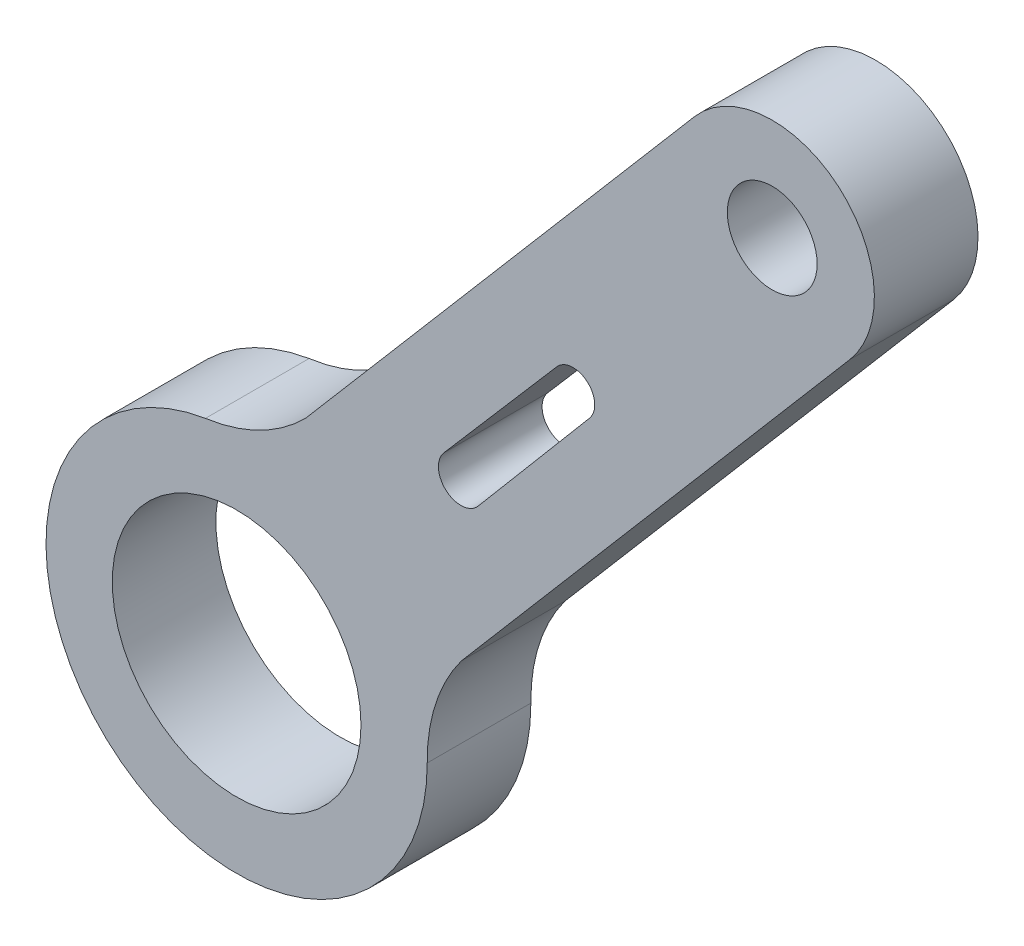
SolidWorks part; units mm, degrees
ref_plane "Front Plane" through (0, 0, 0) normal (0, 0, 1) x (1, 0, 0)
ref_plane "Top Plane" through (0, 0, 0) normal (0, 1, 0) x (1, 0, 0)
ref_plane "Right Plane" through (0, 0, 0) normal (1, 0, 0) x (0, 0, -1)
sketch "Model" plane through (0, 0, 0) normal (0, 0, 1) x (1, 0, 0)
  line L0 (58.0684, 48.5339) -> (46.8301, 35.3658)
  line L1 (47.3143, 39.4872) -> (50.5441, 43.3105)
  line L2 (49.5899, 44.1172) -> (46.3215, 40.3264)
  line L3 (42.3417, 39.2174) -> (53.58, 52.3854)
  line L4 (40.3259, 32.3001) -> (55.8294, 50.4657) construction
  line L5 (53.58, 52.3854) -> (58.0788, 48.546) construction
  line L7 (58.0684, 48.5339) -> (58.0788, 48.546)
  circle A0 centre (40.3259, 32.3001) radius 3.6
  circle A1 centre (55.8294, 50.4657) radius 1.3
  arc A2 (39.4242, 37.7438) -> (42.3417, 39.2174) centre (38.7526, 42.6984) ccw
  arc A3 (39.4242, 37.7438) -> (45.8437, 32.3149) centre (40.3259, 32.3001) ccw
  arc A4 (46.8301, 35.3658) -> (45.8437, 32.3149) centre (50.8431, 32.3835) ccw
  arc A5 (53.58, 52.3854) -> (58.0788, 48.546) centre (55.8294, 50.4657) cw
  arc A6 (50.5441, 43.3105) -> (49.5899, 44.1172) centre (50.067, 43.7138) ccw
  arc A7 (46.3215, 40.3264) -> (47.3143, 39.4872) centre (46.8179, 39.9068) ccw
extrude "Boss-Extrude1" add sketch "Model" along normal blind 3
